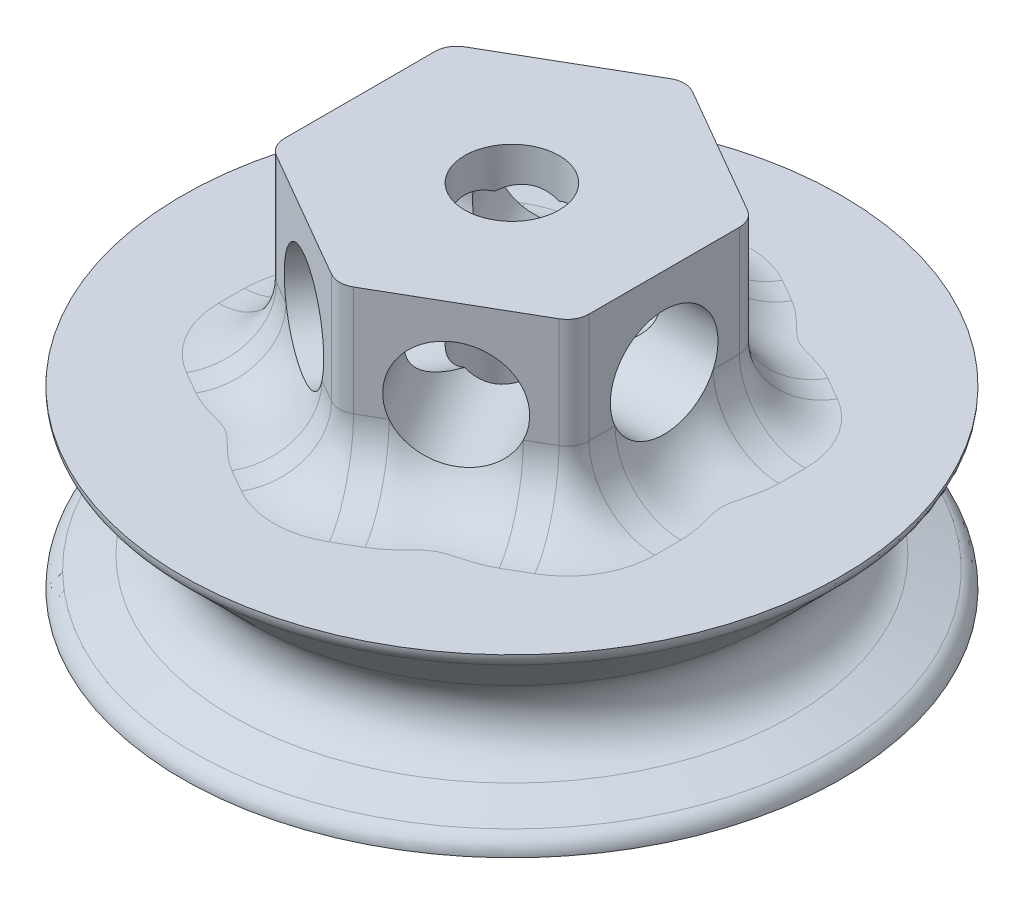
SolidWorks part; units mm, degrees
ref_plane "Front Plane" through (0, 0, 0) normal (0, 0, 1) x (1, 0, 0)
ref_plane "Top Plane" through (0, 0, 0) normal (0, 1, 0) x (1, 0, 0)
ref_plane "Right Plane" through (0, 0, 0) normal (1, 0, 0) x (0, 0, -1)
sketch "Sketch1" plane through (0, 0, 0) normal (0, 0, 1) x (1, 0, 0)
  line L0 (-2.15, 0) -> (-2.15, 8)
  line L1 (-2.15, 8) -> (-15, 8)
  line L2 (-14.7657, 7.4343) -> (-11.9858, 4.6544)
  line L3 (-12.7455, 1.3503) -> (-14.4618, 0.756)
  line L4 (-15, 0) -> (-2.15, 0)
  line L5 (0, 0) -> (0, 15.8767) construction
  arc A0 (-15, 8) -> (-14.7657, 7.4343) centre (-14.2, 8) ccw
  arc A1 (-11.9858, 4.6544) -> (-12.7455, 1.3503) centre (-13.4, 3.2402) cw
  arc A2 (-15, 0) -> (-14.4618, 0.756) centre (-14.2, 0) cw
  dimension "D1" = 8
  dimension "D4" = 2
  dimension "D5" = 0.8
  dimension "D2" = 2.15
  dimension "D3" = 15
  dimension "D6" = 45
  dimension "D7" = 13.4
revolve "Revolve1" add sketch "Sketch1" angle 360 about L5
sketch "Sketch2" plane through (0, 8, 0) normal (0, 1, 0) x (1, 0, 0)
  line L1 (0, 8) -> (-6.9282, 4)
  line L2 (-6.9282, 4) -> (-6.9282, -4)
  line L3 (-6.9282, -4) -> (0, -8)
  line L4 (0, -8) -> (6.9282, -4)
  line L5 (6.9282, -4) -> (6.9282, 4)
  line L6 (6.9282, 4) -> (0, 8)
  circle A0 centre (0, 0) radius 2.15
  circle A1 centre (0, 0) radius 6.9282 construction
  circle A2 centre (0, 0) radius 2.15 construction
  dimension "D1" = 8
extrude "Boss-Extrude1" add sketch "Sketch2" along normal blind 8
sketch "Sketch3" plane through (-3.4641, 0, 6) normal (-0.5, 0, 0.866) x (0.866, 0, 0.5)
  line L0 (-4, 16) -> (4, 8) construction
  circle A0 centre (0, 12) radius 2.45
  dimension "D1" = 4.9
extrude "Cut-Extrude1" cut sketch "Sketch3" against normal through all
ref_axis "Axis1" through (0, 16, 0) along (0, -1, 0)
pattern_circular "CirPattern1" count 3 over 360 about axis through (0, 16, 0) along (0, -1, 0) of "Cut-Extrude1"
fillet "Fillet1" radius 1 6 edges at (-6.9282, 12, -4) (0, 12, -8) (6.9282, 12, -4) (6.9282, 12, 4) (0, 12, 8) (-6.9282, 12, 4)
fillet "Fillet2" radius 3 12 edges at (-6.7942, 8, 3.9226) (-6.9282, 8, 0) (-6.7942, 8, -3.9226) (-3.4641, 8, -6) (0, 8, -7.8453) (3.4641, 8, -6) (6.7942, 8, -3.9226) (6.9282, 8, 0) (6.7942, 8, 3.9226) (3.4641, 8, 6) (0, 8, 7.8453) (-3.4641, 8, 6)
